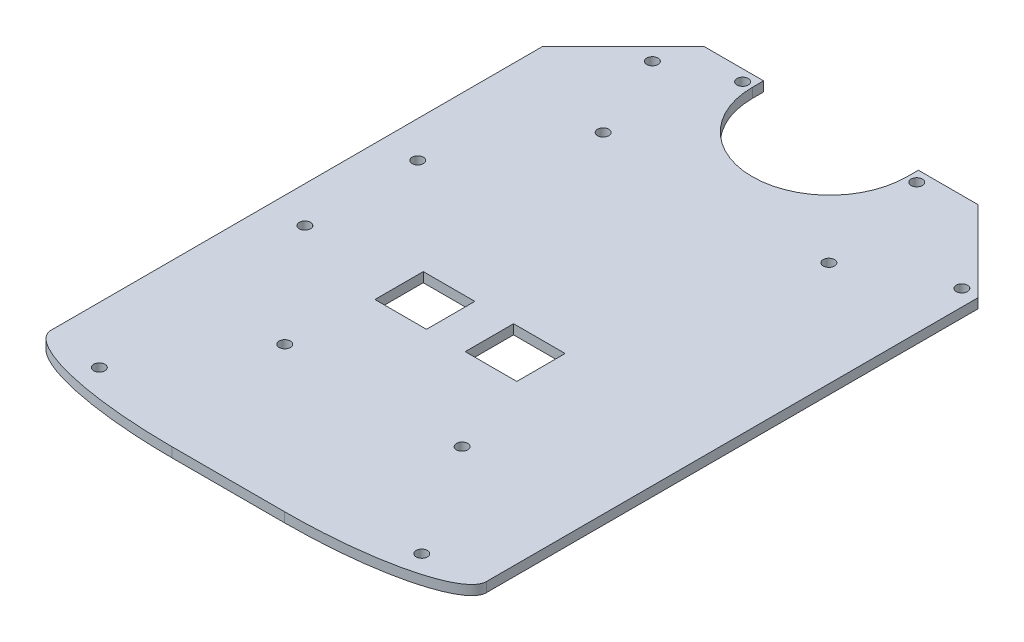
SolidWorks part; units mm, degrees
material "Balsa"
ref_plane "Alzado" through (0, 0, 0) normal (0, 0, 1) x (1, 0, 0)
ref_plane "Planta" through (0, 0, 0) normal (0, 1, 0) x (1, 0, 0)
ref_plane "Vista lateral" through (0, 0, 0) normal (1, 0, 0) x (0, 0, -1)
sketch "Sketch2" plane through (0, 0, 0) normal (0, 1, 0) x (1, 0, 0)
  line L1 (-67.5, 95) -> (67.5, 95)
  line L2 (-67.5, 95) -> (-67.5, -95)
  line L3 (-67.5, -95) -> (67.5, -95)
  line L4 (67.5, 95) -> (67.5, -95)
  line L5 (-67.5, 95) -> (67.5, -95) construction
  line L6 (-67.5, -95) -> (67.5, 95) construction
  point P0 (0, 0)
  dimension "D1" = 135
  dimension "D2" = 190
extrude "Boss-Extrude2" add sketch "Sketch2" along normal blind 3
sketch "Sketch3" plane through (0, 3, 0) normal (0, 1, 0) x (1, 0, 0)
  line L0 (0, -95) -> (0, 95) construction
  line L1 (-67.5, -95) -> (67.5, -95) construction
  line L2 (67.5, 95) -> (-67.5, 95) construction
  line L3 (-67.5, 95) -> (-67.5, -95) construction
  line L4 (-67.5, -95) -> (67.5, -95) construction
  circle A0 centre (-27.5, -50) radius 1.75
  circle A1 centre (27.5, -50) radius 1.75
  circle A2 centre (-50, -85) radius 1.75
  circle A3 centre (50, -85) radius 1.75
  dimension "D1" = 40
  dimension "D3" = 3.5
  dimension "D4" = 10
  dimension "D2" = 45
  dimension "D5" = 50
extrude "Cut-Extrude1" cut sketch "Sketch3" against normal through all
fillet "Fillet1" radius 12.5 1 edges at (-67.5, 1.5, 95) second distance 50 first distance on face at (-67.5, 1.5, 0)
fillet "Fillet2" radius 12.5 1 edges at (67.5, 1.5, 95) second distance 50 first distance on face at (67.5, 1.5, 0)
chamfer "Chamfer2" distance 25 angle 45 1 edges at (67.5, 1.5, -95)
chamfer "Chamfer3" distance 25 angle 45 1 edges at (-67.5, 1.5, -95)
sketch "Sketch7" plane through (0, 3, 0) normal (0, 1, 0) x (1, 0, 0)
  line L0 (42.5, 95) -> (-42.5, 95) construction
  line L1 (24, 91.5) -> (24, 95)
  line L2 (24, 95) -> (-24, 95)
  line L3 (-24, 95) -> (-24, 91.5)
  arc A0 (-24, 91.5) -> (24, 91.5) centre (0, 91.5) ccw
  dimension "D2" = 48
  dimension "D1" = 3.5
extrude "Cut-Extrude5" cut sketch "Sketch7" against normal through all
sketch "Sketch8" plane through (0, 3, 0) normal (0, 1, 0) x (1, 0, 0)
  line L0 (-27, 91.5) -> (27, 91.5) construction
  line L1 (-24, 95) -> (-42.5, 95) construction
  line L2 (-24, 95) -> (24, 95) construction
  line L3 (0, -95) -> (0, 95) construction
  line L4 (-17.5, -95) -> (17.5, -95) construction
  circle A0 centre (-27, 91.5) radius 1.75
  circle A1 centre (27, 91.5) radius 1.75
  point P14 (0, 91.5)
  dimension "D1" = 3.5
  dimension "D2" = 3.5
  dimension "D3" = 54
extrude "Cut-Extrude6" cut sketch "Sketch8" against normal through all
sketch "Sketch9" plane through (0, 3, 0) normal (0, 1, 0) x (1, 0, 0)
  line L0 (-17.5, -95) -> (17.5, -95) construction
  line L1 (0, -95) -> (0, 67.5) construction
  line L2 (-56.25, 20) -> (-56.25, -15) construction
  line L4 (-67.5, 70) -> (-67.5, -82.5) construction
  circle A0 centre (-56.25, -15) radius 1.75
  circle A1 centre (-35, 56.25) radius 1.75
  arc A3 (-24, 91.5) -> (24, 91.5) centre (0, 91.5) ccw construction
  circle A4 centre (-56.25, 20) radius 1.75
  circle A5 centre (35, 56.25) radius 1.75
  dimension "D1" = 3.5
  dimension "D2" = 80
  dimension "D3" = 56.25
  dimension "D4" = 35
  dimension "D5" = 21.25
  dimension "D6" = 36.25
extrude "Cut-Extrude7" cut sketch "Sketch9" against normal through all
sketch "Sketch11" plane through (0, 3, 0) normal (0, 1, 0) x (1, 0, 0)
  line L0 (42.5, 95) -> (24, 95) construction
  line L1 (67.5, -82.5) -> (67.5, 70) construction
  line L4 (-24, 95) -> (-42.5, 95) construction
  circle A0 centre (62.5, 70) radius 1.75
  circle A2 centre (-46.5, 83) radius 1.75
  dimension "D3" = 3.5
  dimension "D1" = 25
  dimension "D2" = 5
  dimension "D4" = 12
  dimension "D5" = 4
extrude "Cut-Extrude8" cut sketch "Sketch11" against normal through all
sketch "Sketch12" plane through (0, 3, 0) normal (0, 1, 0) x (1, 0, 0)
  line L0 (-17.5, -95) -> (17.5, -95) construction
  line L1 (-25.535, -9) -> (-9.535, -9)
  line L2 (-25.535, -9) -> (-25.535, -24)
  line L3 (-25.535, -24) -> (-9.535, -24)
  line L4 (-9.535, -9) -> (-9.535, -24)
  line L5 (2.465, -9) -> (18.465, -9)
  line L6 (2.465, -9) -> (2.465, -24)
  line L7 (2.465, -24) -> (18.465, -24)
  line L8 (18.465, -9) -> (18.465, -24)
  dimension "D1" = 71
  dimension "D2" = 16
  dimension "D3" = 12
  dimension "D4" = 8.035
  dimension "D5" = 15
extrude "Cut-Extrude9" cut sketch "Sketch12" against normal through all
